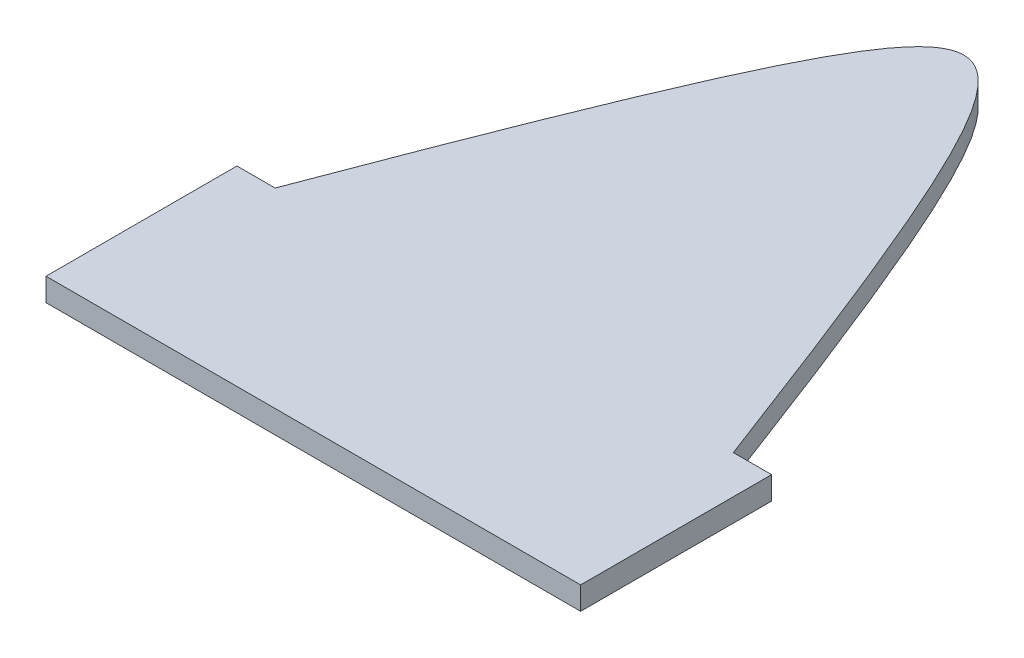
SolidWorks part; units mm, degrees
ref_plane "Front Plane" through (0, 0, 0) normal (0, 0, 1) x (1, 0, 0)
ref_plane "Top Plane" through (0, 0, 0) normal (0, 1, 0) x (1, 0, 0)
ref_plane "Right Plane" through (0, 0, 0) normal (1, 0, 0) x (0, 0, -1)
sketch "Sketch1" plane through (0, 0, 0) normal (0, 1, 0) x (1, 0, 0)
  line L0 (-30, 0) -> (30, 0) construction
  line L1 (-30, 60) -> (31.5332, 60) construction
  line L2 (-30, 0) -> (-35, 0)
  line L3 (-35, 0) -> (-35, -25)
  line L4 (-35, -25) -> (35, -25)
  line L5 (35, -25) -> (35, 0)
  line L6 (35, 0) -> (30, 0)
  conic Q0 (-30, 0) -> (30, 0) control (0, 79.6775) rho 0.755106
  dimension "D1" = 60
  dimension "D2" = 60
  dimension "D3" = 5
  dimension "D4" = 5
  dimension "D5" = 25
base flange "Base-Flange1" sketch "Sketch1" thickness 3 reverse thickness direction no parameters "D1"=7.5
sketch "Sketch8" plane through (0, 0, 0) normal (0, 1, 0) x (1, 0, 0)
  line L0 (-32.5, 0) -> (32.5, 0) construction
  line L1 (-30, 0) -> (-35, 0) construction
  line L2 (35, 0) -> (30, 0) construction
sketch "Bend-Lines1" [suppressed] plane through (0, 0, 0) normal (0, 1, 0) x (1, 0, 0)
sketch "Bounding-Box1" [suppressed] plane through (0, 0, 0) normal (0, 1, 0) x (1, 0, 0)
sheet metal parameters "Sheet-Metal1" thickness 3 parameters "D1"=7.5
flat pattern "Flat-Pattern1" [suppressed]
sketch "Bend-Lines2" plane through (0, 0, 0) normal (0, 1, 0) x (1, 0, 0)
sketch3d "Bounding-Box2" [suppressed]
  line L0 (-35.0001, 0, 0) -> (-35, -85.1649, 0) construction
  line L1 (34.9999, 0, 0) -> (35, -85.1649, 0) construction
  line L2 (-35.0001, 0, 0) -> (34.9999, 0, 0) construction
  line L3 (-35, -85.1649, 0) -> (35, -85.1649, 0) construction
